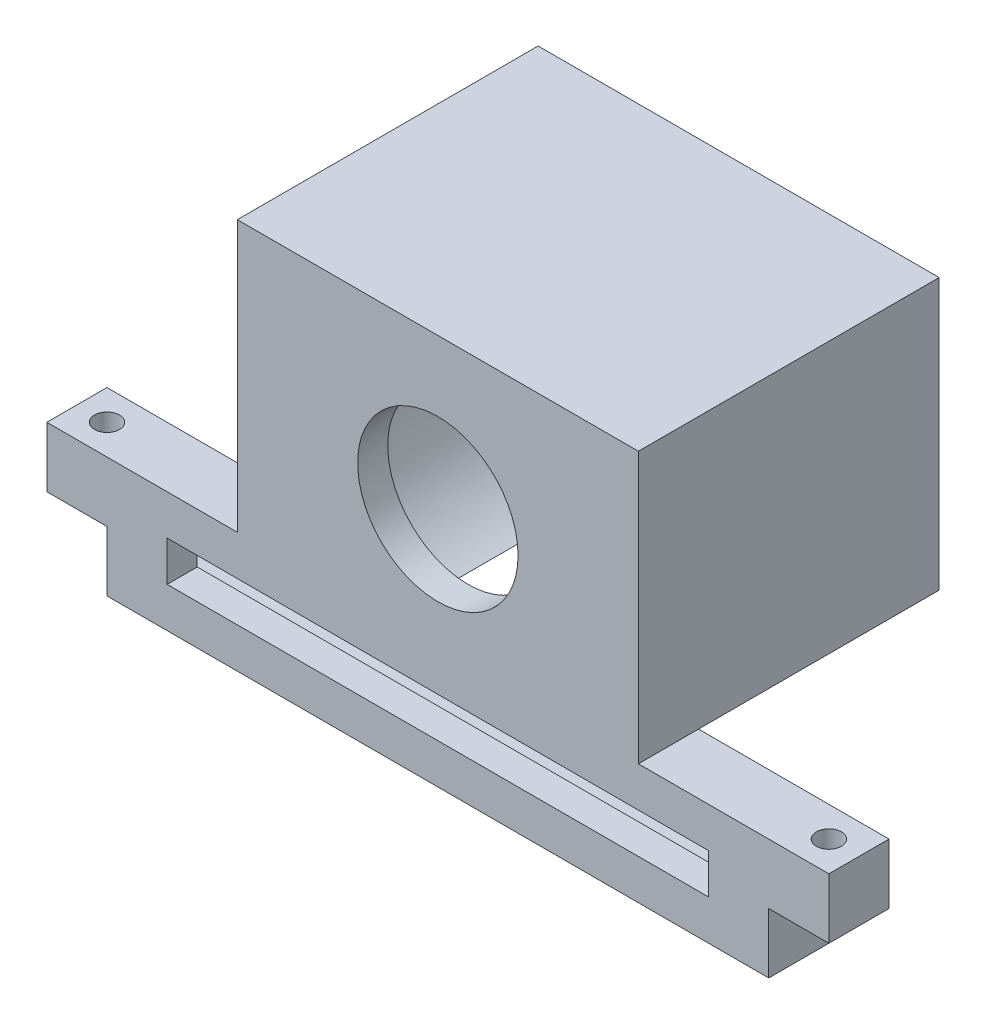
SolidWorks part; units mm, degrees
material "1060 Alloy"
ref_plane "Front Plane" through (0, 0, 0) normal (0, 0, 1) x (1, 0, 0)
ref_plane "Top Plane" through (0, 0, 0) normal (0, 1, 0) x (1, 0, 0)
ref_plane "Right Plane" through (0, 0, 0) normal (1, 0, 0) x (0, 0, -1)
sketch "Sketch1" plane through (0, 0, 0) normal (0, 0, 1) x (1, 0, 0)
  line L0 (19, 33) -> (59, 33)
  line L1 (6, 0) -> (6, -6)
  line L2 (59, 33) -> (59, 6)
  line L3 (19, 33) -> (19, 6)
  line L4 (12, 2) -> (66, 2)
  line L5 (12, 2) -> (12, -2)
  line L6 (12, -2) -> (66, -2)
  line L7 (66, 2) -> (66, -2)
  line L8 (6, -6) -> (72, -6)
  line L9 (72, -6) -> (72, 0)
  line L10 (6, 0) -> (0, 0)
  line L11 (0, 0) -> (0, 6)
  line L12 (0, 6) -> (19, 6)
  line L13 (59, 6) -> (78, 6)
  line L14 (78, 6) -> (78, 0)
  line L15 (78, 0) -> (72, 0)
  circle A0 centre (39, 18) radius 8
  dimension "D4" = 16
  dimension "D1" = 4
  dimension "D2" = 54
  dimension "D3" = 4
  dimension "D5" = 6
  dimension "D6" = 6
  dimension "D7" = 40
  dimension "D8" = 20
  dimension "D9" = 18
  dimension "D10" = 2
  dimension "D11" = 7
  dimension "D12" = 6
  dimension "D13" = 4
  dimension "D14" = 33
extrude "Boss-Extrude1" add sketch "Sketch1" along normal blind 30
sketch "Sketch3" plane through (0, 0, 0) normal (0, 0, -1) x (-1, 0, 0)
  circle A0 centre (-39, 18) radius 13
  dimension "D1" = 26
extrude "Cut-Extrude2" cut sketch "Sketch3" against normal offset from surface (27 mm away) 3 up to face at (39, 0, 30)
hole_wizard "Tap Drill for M3 Tap2" positions "Sketch5" profile "Sketch4" hole size "M3" standard "ISO"
sketch "Sketch5" plane through (38.1016, 0, -22.7468) normal (0, -1, 0) x (-1, 0, 0)
  line L3 (-39.8984, -52.7468) -> (-39.8984, -22.7468) construction
  line L4 (38.1016, -52.7468) -> (38.1016, -22.7468) construction
  line L5 (-33.8984, -52.7468) -> (-39.8984, -52.7468) construction
  point P0 (35.1016, -49.7468)
  point P2 (-36.8984, -49.7468)
  dimension "D1" = 3
  dimension "D2" = 3
  dimension "D3" = 3
sketch "Sketch4" plane through (3, 0, 27) normal (1, 0, 0) x (0, 0, -1)
  line L0 (0, 0) -> (0, 8.7511)
  line L1 (0, 8.7511) -> (1.25, 8)
  line L2 (1.25, 8) -> (1.25, 0)
  line L5 (1.25, 0) -> (0, 0)
  line L10 (0, 8.7511) -> (-1.25, 8) construction
  line L11 (0, -6.35) -> (0, 107.95) construction
  dimension "Hole Dia." = 2.5
  dimension "Hole Depth" = 8
  dimension "Drill Angle" = 118
sketch "Sketch6" plane through (0, 0, 0) normal (0, 0, -1) x (-1, 0, 0)
  line L2 (-78, 6) -> (0, 6)
  line L3 (-78, 6) -> (-78, -6)
  line L4 (-78, -6) -> (0, -6)
  line L5 (0, 6) -> (0, -6)
extrude "Cut-Extrude3" cut sketch "Sketch6" along direction (0, 0, 1) on the side against the normal offset from surface (24 mm away) 6 up to face at (39, 0, 30)
sketch "Sketch10" plane through (0, 0, 24) normal (0, 0, -1) x (-1, 0, 0)
  line L0 (-12, -2) -> (-66, -2) construction
  line L1 (-68, 3) -> (-10, 3)
  line L2 (-68, 3) -> (-68, -3)
  line L3 (-68, -3) -> (-10, -3)
  line L4 (-10, 3) -> (-10, -3)
  line L5 (-66, 2) -> (-12, 2) construction
  line L6 (-66, -2) -> (-66, 2) construction
  line L7 (-12, 2) -> (-12, -2) construction
  dimension "D1" = 1
  dimension "D2" = 1
  dimension "D3" = 2
  dimension "D4" = 2
extrude "Cut-Extrude5" cut sketch "Sketch10" against normal blind 3
